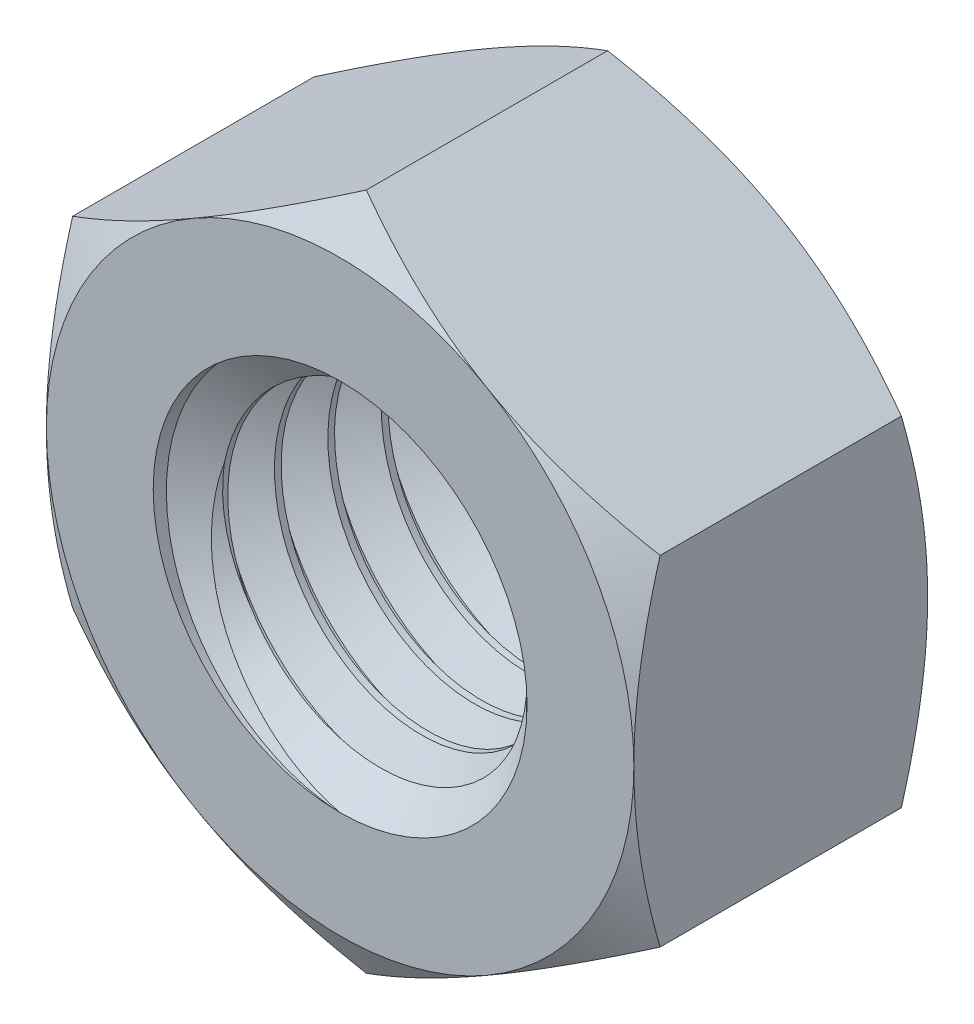
SolidWorks part; units mm, degrees
ref_plane "Front" through (0, 0, 0) normal (0, 0, 1) x (1, 0, 0)
ref_plane "Top" through (0, 0, 0) normal (0, 1, 0) x (1, 0, 0)
ref_plane "Right" through (0, 0, 0) normal (1, 0, 0) x (0, 0, -1)
sketch "Sketch1" plane through (0, 0, 0) normal (0, 0, 1) x (1, 0, 0)
  line L1 (-5.5, 3.1754) -> (-5.5, -3.1754)
  line L2 (-5.5, -3.1754) -> (0, -6.3509)
  line L3 (0, -6.3509) -> (5.5, -3.1754)
  line L4 (5.5, -3.1754) -> (5.5, 3.1754)
  line L5 (5.5, 3.1754) -> (0, 6.3509)
  line L6 (0, 6.3509) -> (-5.5, 3.1754)
  circle A0 centre (0, 0) radius 5.5 construction
  circle A1 centre (0, 0) radius 3.5 construction
  point P10 (0, 3.5)
  dimension "hex" = 11
  dimension "dia" = 7
extrude "Extrude1" add sketch "Sketch1" along normal mid plane 5.5
sketch "Sketch4" plane through (0, 0, -2.75) normal (0, 0, -1) x (-1, 0, 0)
  circle A0 centre (0, 0) radius 3.5 construction
  circle A1 centre (0, 0) radius 3.5
sketch "Sketch10" plane through (0, 0, 2.75) normal (0, 0, 1) x (1, 0, 0)
  circle A0 centre (0, 0) radius 3.5 construction
  circle A1 centre (0, 0) radius 3.5
extrude "Cut-Extrude2" cut sketch "Sketch10" against normal through all draft 45
sketch "Sketch11" plane through (0, 0, -2.75) normal (0, 0, -1) x (-1, 0, 0)
  circle A0 centre (0, 0) radius 3.5 construction
  circle A1 centre (0, 0) radius 3.5
extrude "Cut-Extrude3" cut sketch "Sketch11" against normal through all draft 45
sketch "Sketch13" plane through (0, 0, -2.75) normal (0, 0, -1) x (-1, 0, 0)
  circle A0 centre (0, 0) radius 3.5 construction
  circle A1 centre (0, 0) radius 3.5
extrude "Boss-Extrude1" add sketch "Sketch13" against normal up to vertex (5.5 mm away) separate body up to point (-5.5, 3.1754, 2.75)
curve "Helix/Spiral3" pitch 1 height 5.5 turns 5.5
sketch "Sketch12" plane through (0, 0, 0) normal (1, 0, 0) x (0, 0, -1)
  line L0 (3.625, 3.5) -> (2.75, 3.5)
  line L1 (3.625, 3.5) -> (3.25, 2.8505)
  line L2 (3.25, 2.8505) -> (3.125, 2.8505)
  line L3 (3.125, 2.8505) -> (2.75, 3.5)
  line L4 (3.1875, 2.8505) -> (3.1875, 3.5) construction
  line L5 (2.9375, 3.1752) -> (3.4375, 3.1752) construction
  dimension "D1" = 60
  dimension "D2" = 0.125
  dimension "D3" = 0.5
sweep "Cut-Sweep1" cut profiles "Sketch12" path "Helix/Spiral3"
combine bodies "Combine1" operation type subtract main body 116 bodies to subtract 118
sketch "Sketch7" plane through (0, 0, 2.75) normal (0, 0, 1) x (1, 0, 0)
  circle A0 centre (0, 0) radius 5.5 construction
  circle A1 centre (0, 0) radius 5.5
extrude "Extrude2" cut sketch "Sketch7" against normal blind 25.4 draft 60 flip side to cut
mirror "Mirror2" about plane through (0, 0, 0) normal (0, 0, 1) of "Extrude2"
sketch "Sketch8" plane through (0, 0, 2.75) normal (0, 0, 1) x (1, 0, 0)
  line L0 (-2.4749, 2.4749) -> (0, 0) construction
  line L1 (0, -3.2666) -> (0, 3.2666) construction
  circle A1 centre (0, 0) radius 3.5 construction
  point P0 (-2.4749, 2.4749)
  dimension "D1" = 45
sketch "Sketch14" plane through (0, 0, 2.75) normal (0, 0, 1) x (1, 0, 0)
  line L0 (0, 0) -> (-3.5, 0) construction
  arc A0 (0, 3.5) -> (0, -3.5) centre (0, 0) ccw construction
equation "\"D3@Helix/Spiral3\" = \"length@Extrude1\" "
equation "\"D2@Sketch12\" = \"D4@Helix/Spiral3\"*.125"
equation "\"D3@Sketch12\" = \"D4@Helix/Spiral3\"*.50"
